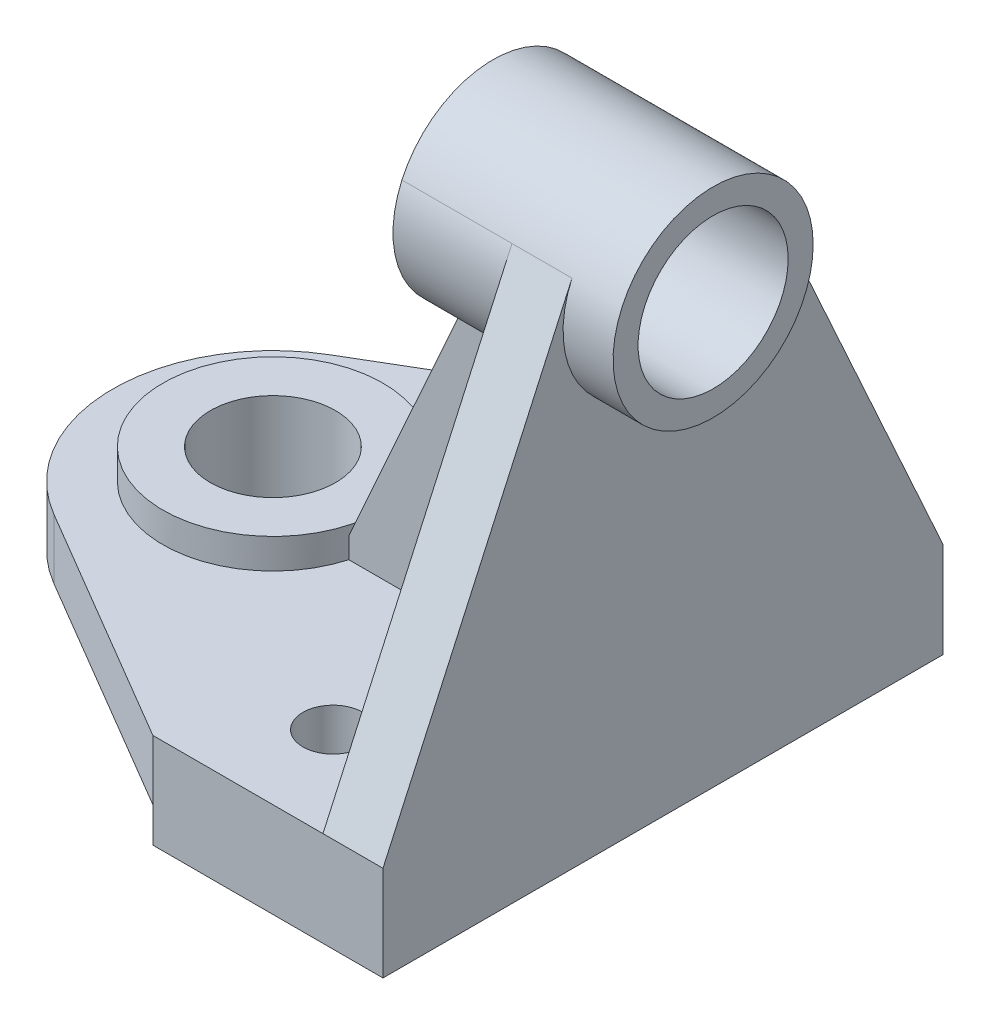
SolidWorks part; units mm, degrees
ref_plane "Front Plane" through (0, 0, 0) normal (0, 0, 1) x (1, 0, 0)
ref_plane "Top Plane" through (0, 0, 0) normal (0, 1, 0) x (1, 0, 0)
ref_plane "Right Plane" through (0, 0, 0) normal (1, 0, 0) x (0, 0, -1)
sketch "Sketch2" plane through (0, 0, 0) normal (0, 1, 0) x (1, 0, 0)
  line L0 (2.2885, 0) -> (50002.2885, 0) construction
  line L1 (0, 3.0768) -> (0, 50003.0768) construction
  line L2 (66, 56) -> (32, 56)
  line L3 (66, -56) -> (32, -56)
  line L8 (32, 56) -> (-16.2462, 27.5692)
  line L9 (32, -56) -> (-16.2462, -27.5692)
  line L10 (32, 56) -> (32, -56)
  line L11 (66, 56) -> (66, -56)
  circle A0 centre (0, 0) radius 12.5
  circle A1 centre (0, 0) radius 22
  arc A2 (-16.2462, 27.5692) -> (-16.2462, -27.5692) centre (0, 0) ccw
  circle A3 centre (49, -37) radius 6
  circle A4 centre (49, 37) radius 6
  point P12 (78, 0)
  dimension "D1" = 25
  dimension "D2" = 44
  dimension "D3" = 64
  dimension "D8" = 12
  dimension "D4" = 112
  dimension "D5" = 66
  dimension "D6" = 49
  dimension "D7" = 34
  dimension "D10" = 19
extrude "Boss-Extrude1" add sketch "Sketch2" against normal blind 19 contours L2 L10 L3 L11 A4 A3 region at (49, 0, 0)
extrude "Boss-Extrude2" add sketch "Sketch2<3>" against normal blind 12 contours L8 A2 L9 L10 A1 region at (30.71, 0, 0)
sketch "Sketch2<3>" plane through (0, 0, 0) normal (0, 1, 0) x (1, 0, 0) same geometry as "Sketch2"
extrude "Boss-Extrude3" add sketch "Sketch2<4>" along normal blind 6 and the other way blind 38 contours A1 A0 region at (-21.3777, 0, 0)
sketch "Sketch2<4>" plane through (0, 0, 0) normal (0, 1, 0) x (1, 0, 0) same geometry as "Sketch2"
sketch "Sketch3" plane through (66, 0, 0) normal (1, 0, 0) x (0, 0, -1)
  line L0 (-56, 0) -> (-56, -19)
  line L1 (-56, -19) -> (56, -19)
  line L2 (56, -19) -> (56, 0)
  line L3 (-56, 0) -> (-18.2123, 83.2652)
  line L4 (56, 0) -> (18.2123, 83.2652)
  circle A0 centre (0, 75) radius 15
  circle A1 centre (0, 75) radius 20
  line M3 (56, 0) -> (-56, 0)
  line M4 (-56, 0) -> (-56, -19)
  line M5 (-56, -19) -> (56, -19)
  line M6 (56, -19) -> (56, 0)
  dimension "D1" = 75
  dimension "D2" = 30
  dimension "D3" = 40
extrude "Boss-Extrude4" add sketch "Sketch3" along normal blind 12 contours A1 L3 L4 M3 | M6 M3 M4 M5 region at (66, -9.5, 0) region at (66, 27.9976, 0)
extrude "Boss-Extrude5" add sketch "Sketch3<3>" along normal mid plane 44 contours A1 A0 region at (66, 94.4343, 0)
sketch "Sketch3<3>" plane through (66, 0, 0) normal (1, 0, 0) x (0, 0, -1) same geometry as "Sketch3"
sketch "Sketch4" plane through (0, 0, 0) normal (0, 0, 1) x (1, 0, 0)
  line L0 (44, 55) -> (22, 6)
  line L1 (22, 6) -> (-22, 6) construction
rib "Rib1" sketch "Sketch4" sketch "Sketch4" thickness 12 extrusion direction parallel to sketch draft on no parameters "D1"=12
